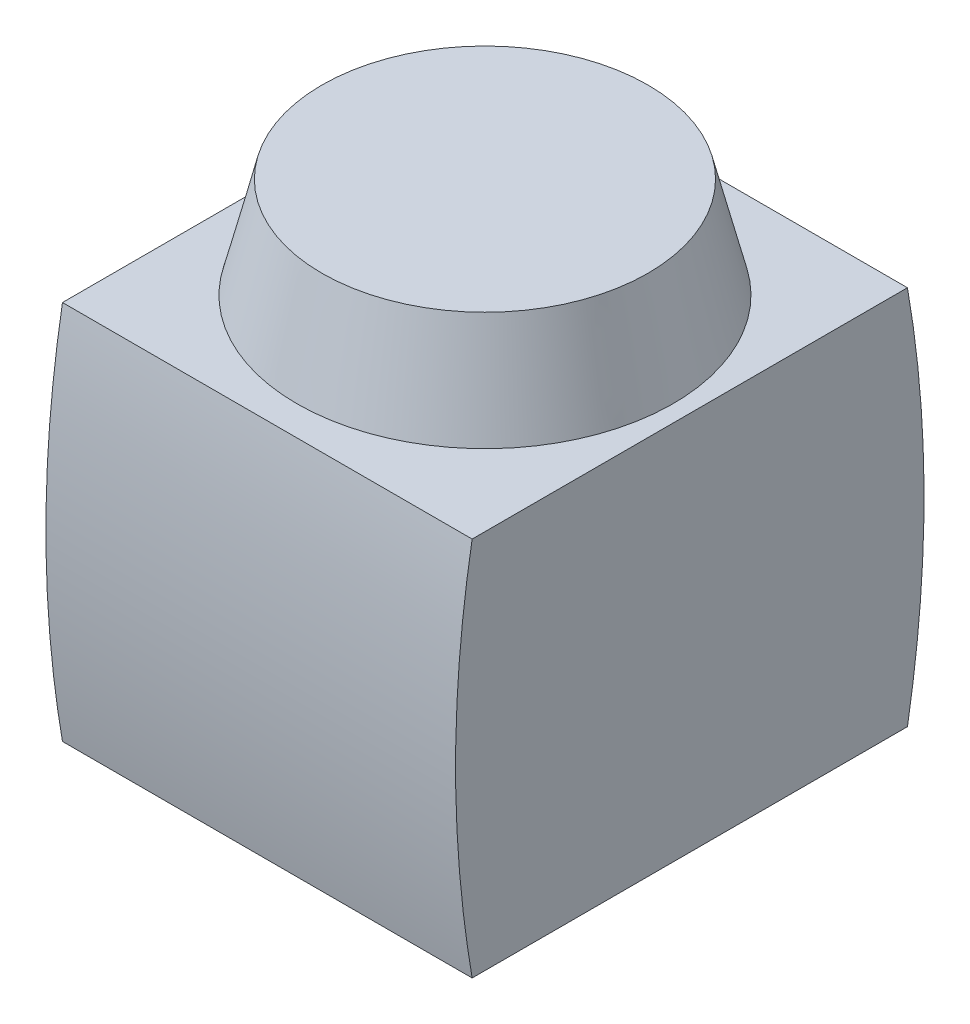
SolidWorks part; units mm, degrees
ref_plane "Front Plane" through (0, 0, 0) normal (0, 0, 1) x (1, 0, 0)
ref_plane "Top Plane" through (0, 0, 0) normal (0, 1, 0) x (1, 0, 0)
ref_plane "Right Plane" through (0, 0, 0) normal (1, 0, 0) x (0, 0, -1)
sketch "Sketch1" plane through (0, 0, 0) normal (1, 0, 0) x (0, 0, -1)
  line L0 (-1.105, -0.965) -> (1.105, -0.965)
  line L1 (-1.105, 0.965) -> (-1.105, -0.965) construction
  line L2 (1.105, 0.965) -> (-1.105, 0.965)
  line L3 (1.105, -0.965) -> (1.105, 0.965) construction
  line L4 (0, 0.965) -> (0, -0.965) construction
  spline S0 degree 2 poles (-1.105, 0.965) (-1.2733, 0.0094) (-1.105, -0.965) knots 0 0 0 1 1 1
  spline S1 degree 2 poles (1.105, 0.965) (1.2733, 0.0094) (1.105, -0.965) knots 0 0 0 1 1 1
  point P6 (0, 0)
  point P7 (0, 0)
  dimension "D1" = 2.21
  dimension "D2" = 1.93
extrude "Boss-Extrude1" add sketch "Sketch1" along normal blind 1.04 and the other way blind 1.04
sketch "Sketch2" plane through (0, 0.965, 0) normal (0, 1, 0) x (1, 0, 0)
  circle A0 centre (0, 0) radius 0.955
  dimension "D1" = 1.91
extrude "Boss-Extrude2" add sketch "Sketch2" along normal blind 0.51 draft 14
